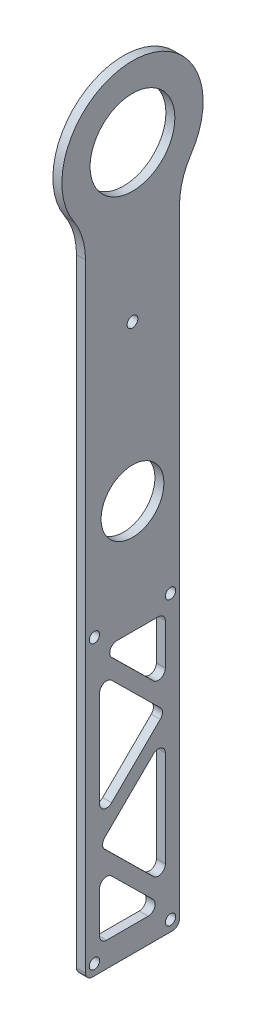
SolidWorks part; units mm, degrees
material "6061 Alloy"
ref_plane "Front Plane" through (0, 0, 0) normal (0, 0, 1) x (1, 0, 0)
ref_plane "Top Plane" through (0, 0, 0) normal (0, 1, 0) x (1, 0, 0)
ref_plane "Right Plane" through (0, 0, 0) normal (1, 0, 0) x (0, 0, -1)
sketch "Sketch1" plane through (0, 0, 0) normal (1, 0, 0) x (0, 0, -1)
  line L0 (-13.4747, 0) -> (13.4747, 0) construction
  line L1 (0, 0) -> (0, 35) construction
  line L2 (-13.4747, 0) -> (0, 35) construction
  line L3 (0, 35) -> (13.4747, 0) construction
  line L4 (13.4747, 0) -> (-13.4747, 0) construction
  line L5 (16.645, -5) -> (-16.645, -5) construction
  line L6 (-20.7574, -5) -> (-10.3702, 21.9802) construction
  line L7 (0, 48.9165) -> (1.1006, 46.0579) construction
  line L8 (0, 35) -> (0, 46.1125) construction
  line L9 (0, 35) -> (0, 46.1125) construction
  line L12 (-7.5, 35) -> (-7.5, 43.1999) construction
  line L13 (7.5, 35) -> (7.5, 43.1999) construction
  line L14 (-7.5, 35) -> (-7.5, 29.4356) construction
  line L15 (7.5, 35) -> (7.5, 29.4356) construction
  line L16 (-13.4747, 0) -> (13.4747, 0) construction
  line L17 (-13.4747, 0) -> (-13.4747, -100) construction
  line L18 (13.4747, 0) -> (13.4747, -100) construction
  line L19 (-13.4747, -100) -> (13.4747, -100) construction
  line L20 (-16.645, -5) -> (16.645, -5)
  line L21 (-20.7574, -5) -> (-20.7574, -103.81) construction
  line L22 (20.7574, -5) -> (20.7574, -103.81) construction
  line L23 (-16.645, -103.81) -> (16.645, -103.81)
  line L24 (-10.3702, 21.9802) -> (-8.2317, 27.535) construction
  line L25 (-7.5, 29.4356) -> (-6.6746, 31.5795) construction
  line L26 (-20.7574, -5) -> (0, 48.9165) construction
  line L27 (8.2317, 27.535) -> (10.3702, 21.9802) construction
  line L28 (10.3702, 21.9802) -> (20.7574, -5) construction
  line L29 (0, 48.9165) -> (20.7574, -5) construction
  line L30 (-7.5, 43.1999) -> (-7.5, 49.8595) construction
  line L31 (-7.5, 49.8595) -> (-7.5, 145) construction
  line L32 (7.5, 43.1999) -> (7.5, 49.8595) construction
  line L33 (7.5, 49.8595) -> (7.5, 145) construction
  line L34 (-8.2317, 27.535) -> (-7.5, 29.4356) construction
  line L35 (-6.6746, 31.5795) -> (-1.1006, 46.0579) construction
  line L36 (-1.1006, 46.0579) -> (0, 48.9165) construction
  line L37 (1.1006, 46.0579) -> (6.6746, 31.5795) construction
  line L38 (6.6746, 31.5795) -> (7.5, 29.4356) construction
  line L39 (7.5, 29.4356) -> (8.2317, 27.535) construction
  line L40 (0, 46.1125) -> (0, 48.9165) construction
  line L41 (0, 48.9165) -> (0, 145) construction
  line L42 (0, 46.1125) -> (0, 48.9165) construction
  line L43 (0, 48.9165) -> (0, 145) construction
  line L44 (-20.7574, -103.81) -> (-16.645, -103.81) construction
  line L45 (16.645, -103.81) -> (20.7574, -103.81) construction
  line L46 (-16.645, -103.81) -> (-16.645, 126.3467)
  line L47 (16.645, -103.81) -> (16.645, 126.3467)
  line L48 (-16.645, -5) -> (-20.7574, -5) construction
  line L49 (20.7574, -5) -> (-20.7574, -5) construction
  line L50 (-20.7574, -5) -> (-16.645, -5) construction
  line L51 (20.7574, -5) -> (16.645, -5) construction
  line L52 (16.645, -5) -> (20.7574, -5) construction
  circle A0 centre (-13.4747, 0) radius 1.8288
  circle A1 centre (0, 35) radius 11.1125
  circle A2 centre (13.4747, 0) radius 1.8288
  circle A3 centre (0, 145) radius 3 construction
  arc A6 (-7.5, 35) -> (-6.6746, 31.5795) centre (0, 35) ccw construction
  arc A7 (7.5, 145) -> (-7.5, 145) centre (0, 145) ccw construction
  circle A8 centre (-13.4747, -100) radius 1.8288
  circle A9 centre (13.4747, -100) radius 1.8288
  circle A17 centre (0, 145) radius 15
  arc A18 (16.645, 126.3467) -> (-16.645, 126.3467) centre (0, 145) ccw
  arc A19 (10.3702, 21.9802) -> (7.5, 49.8595) centre (0, 35) ccw construction
  arc A20 (-10.3702, 21.9802) -> (-5.9803, 19.4664) centre (0, 35) ccw construction
  circle A21 centre (0, 35) radius 16.645 construction
  arc A22 (-5.9803, 19.4664) -> (0, 18.355) centre (0, 35) ccw construction
  arc A23 (0, 18.355) -> (5.9803, 19.4664) centre (0, 35) ccw construction
  arc A24 (5.9803, 19.4664) -> (10.3702, 21.9802) centre (0, 35) ccw construction
  arc A25 (0, 51.645) -> (-7.5, 49.8595) centre (0, 35) ccw construction
  arc A26 (-7.5, 49.8595) -> (-10.3702, 21.9802) centre (0, 35) ccw construction
  arc A27 (7.5, 49.8595) -> (0, 51.645) centre (0, 35) ccw construction
  arc A28 (6.6746, 31.5795) -> (7.5, 35) centre (0, 35) ccw construction
  arc A29 (2.6946, 28.0008) -> (6.6746, 31.5795) centre (0, 35) ccw construction
  arc A30 (0, 27.5) -> (2.6946, 28.0008) centre (0, 35) ccw construction
  arc A31 (-2.6946, 28.0008) -> (0, 27.5) centre (0, 35) ccw construction
  arc A32 (-6.6746, 31.5795) -> (-2.6946, 28.0008) centre (0, 35) ccw construction
  arc A33 (-7.5, 121.1515) -> (0, 120) centre (0, 145) ccw construction
  arc A34 (0, 120) -> (7.5, 121.1515) centre (0, 145) ccw construction
  arc A35 (7.5, 121.1515) -> (16.645, 126.3467) centre (0, 145) ccw construction
  arc A36 (-16.645, 126.3467) -> (-7.5, 121.1515) centre (0, 145) ccw construction
  point P4 (0, 0)
  point P14 (0, 90)
  point P34 (0, 145)
  dimension "D3" = 3.6576
  dimension "D4" = 22.225
  dimension "D7" = 6
  dimension "D11" = 16.645
  dimension "D13" = 30
  dimension "D14" = 50
  dimension "D1" = 26.9494
  dimension "D5" = 110
  dimension "D6" = 15
  dimension "D8" = 100
  dimension "D9" = 3.81
  dimension "D10" = 35
  dimension "D2" = 5
extrude "Boss-Extrude1" add sketch "Sketch1" along normal blind 3.175 contours A6 L7 L15 | L21 L23 L22 L5 A9 A8 | L31 A26 L6 L5 L28 A19 L33 A18 A0 A1 A2 | A19 L28 | A26 L6 | L31 A18 L33 A17 | L33 A18 L31 A17 region at (0, 81.9647, 0) region at (0, -54.1118, 0)
sketch "Sketch2" plane through (3.175, 0, 0) normal (1, 0, 0) x (0, 0, -1)
  line L0 (-11.645, -5) -> (11.645, -5) construction
  line L1 (-11.645, -95) -> (11.645, -95) construction
  line L2 (11.645, -95) -> (11.645, -5) construction
  line L3 (-11.645, -95) -> (-11.645, -5) construction
  line L6 (11.645, -38.5118) -> (-11.645, -61.4882) construction
  line L7 (11.645, -5) -> (-11.645, -5)
  line L8 (-11.645, -5) -> (11.645, -27.9764)
  line L9 (11.645, -27.9764) -> (11.645, -5)
  line L10 (-11.645, -12.0236) -> (11.645, -35)
  line L11 (11.645, -35) -> (-11.645, -57.9764)
  line L12 (-11.645, -57.9764) -> (-11.645, -35)
  line L13 (-11.645, -35) -> (-11.645, -12.0236)
  line L14 (-11.645, -72.0236) -> (-11.645, -95)
  line L15 (-11.645, -95) -> (11.645, -95)
  line L16 (11.645, -95) -> (-11.645, -72.0236)
  line L17 (11.645, -42.0236) -> (11.645, -65)
  line L18 (11.645, -65) -> (11.645, -87.9764)
  line L19 (11.645, -87.9764) -> (-11.645, -65)
  line L20 (-11.645, -65) -> (11.645, -42.0236)
  line L21 (16.645, -1056.0877) -> (16.645, 48943.9123) construction
  line L22 (-16.645, -1060.2922) -> (-16.645, 48939.7078) construction
  line L23 (16.645, 23.8875) -> (-16.645, 23.8875) construction
  circle A0 centre (13.4747, 0) radius 1.8288 construction
  circle A1 centre (13.4747, -100) radius 1.8288 construction
  circle A2 centre (0, 35) radius 11.1125 construction
  point P6 (11.645, -50)
  point P10 (0, 23.8875)
  point P21 (0, -50)
  point P41 (0, 0)
  point P43 (0, 0)
  dimension "D1" = 33.29
  dimension "D2" = 5
  dimension "D3" = 5
  dimension "D4" = 5
  dimension "D5" = 5
  dimension "D6" = 2.5
  dimension "D8" = 5
  dimension "D7" = 2
extrude "Cut-Extrude1" cut sketch "Sketch2" against normal up to next
fillet "Fillet3" radius 2.5 14 edges at (1.5875, -57.9764, 11.645) (1.5875, -35, -11.645) (1.5875, -95, -11.645) (1.5875, -72.0236, 11.645) (1.5875, -95, 11.645) (1.5875, -27.9764, -11.645) (1.5875, -5, -11.645) (1.5875, -12.0236, 11.645) (1.5875, -5, 11.645) (1.5875, -87.9764, -11.645) (1.5875, -42.0236, -11.645) (1.5875, -65, 11.645) (1.5875, -103.81, -16.645) (1.5875, -103.81, 16.645)
fillet "Fillet4" radius 25 2 edges at (1.5875, 126.3467, -16.645) (1.5875, 126.3467, 16.645)
hole_wizard "#6 Clearance Hole1" positions "Sketch3" profile "Sketch4" hole size "#6" standard "ANSI Inch" end condition up to next
sketch "Sketch3" plane through (3.175, 0, 0) normal (1, 0, 0) x (0, 0, -1)
  circle A0 centre (0, 35) radius 11.1125 construction
  point P0 (0, 90)
  dimension "D1" = 55
sketch "Sketch4" plane through (3.175, 90, 0) normal (0, 1, 0) x (0, 0, -1)
  line L0 (0, 0) -> (0, 3.175)
  line L1 (0, 3.175) -> (1.8986, 3.175)
  line L2 (1.8986, 3.175) -> (1.8986, 0)
  line L5 (1.8986, 0) -> (0, 0)
  line L11 (0, -6.35) -> (0, 107.95) construction
  dimension "Thru Hole Dia." = 3.7973
  dimension "Thru Hole Depth" = 3.175
